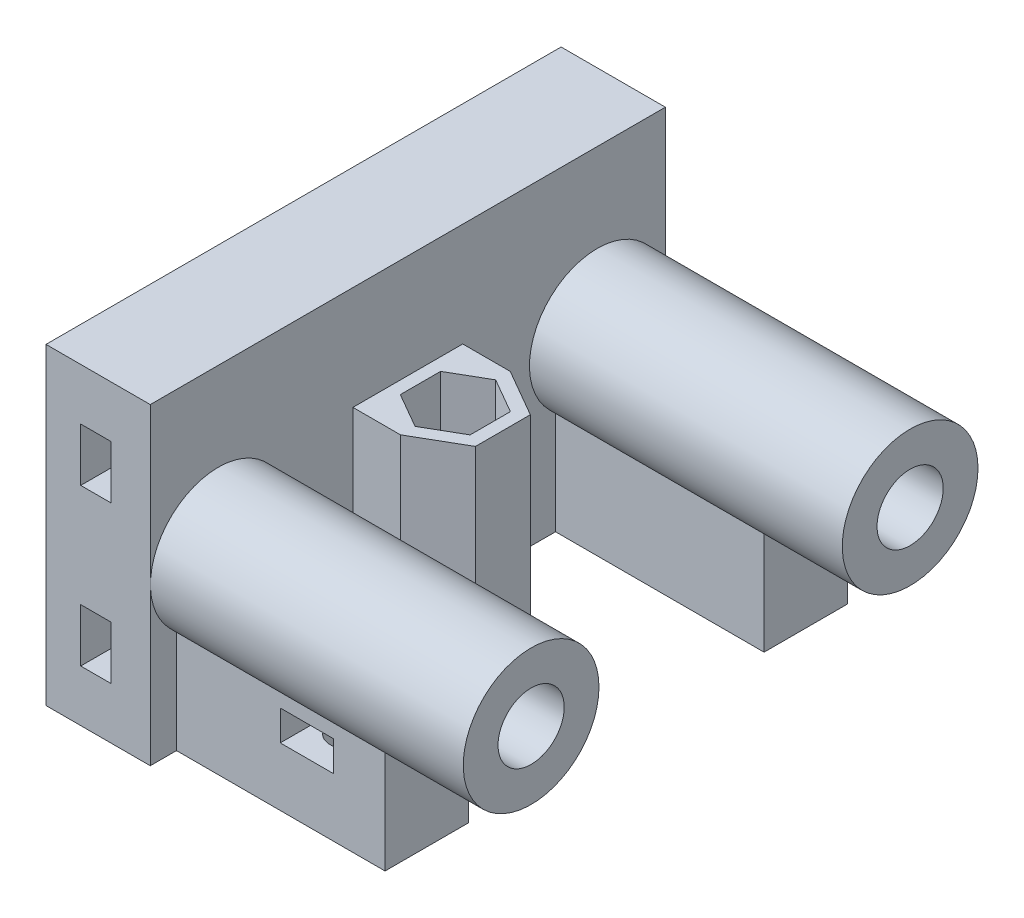
SolidWorks part; units mm, degrees
ref_plane "Front Plane" through (0, 0, 0) normal (0, 0, 1) x (1, 0, 0)
ref_plane "Top Plane" through (0, 0, 0) normal (0, 1, 0) x (1, 0, 0)
ref_plane "Right Plane" through (0, 0, 0) normal (1, 0, 0) x (0, 0, -1)
sketch "Sketch1" plane through (0, 0, 0) normal (1, 0, 0) x (0, 0, -1)
  line L1 (0, 0) -> (88.9, 0)
  line L2 (0, 0) -> (0, 76.2)
  line L3 (0, 76.2) -> (88.9, 76.2)
  line L4 (88.9, 0) -> (88.9, 76.2)
  dimension "D1" = 76.2
  dimension "D2" = 88.9
extrude "Boss-Extrude1" add sketch "Sketch1" along normal blind 25.4
sketch "Sketch2" plane through (0, 0, 0) normal (-1, 0, 0) x (0, 0, 1)
  line L0 (-88.9, 0) -> (-88.9, 76.2) construction
  line L1 (-85.09, 19.05) -> (-88.9, 19.05) construction
  line L2 (-85.09, 57.15) -> (-88.9, 57.15) construction
  line L3 (-44.45, 76.2) -> (-44.45, 0) construction
  line L4 (-88.9, 76.2) -> (0, 76.2) construction
  line L5 (0, 0) -> (-88.9, 0) construction
  circle A0 centre (-85.09, 57.15) radius 4.1021
  circle A1 centre (-85.09, 19.05) radius 4.1021
  circle A2 centre (-3.81, 19.05) radius 4.1021
  circle A3 centre (-3.81, 57.15) radius 4.1021
  dimension "D2" = 8.2042
  dimension "d1" = 19.05
  dimension "D3" = 3.81
  dimension "D4" = 38.1
  dimension "D5" = 81.28
extrude "Cut-Extrude1" cut sketch "Sketch2" against normal blind 19.05 contours A1 | A3 | A2 | A0 region at (0, 19.05, -85.09) region at (0, 19.05, -3.81) region at (0, 57.15, -3.81)
sketch "Sketch3" plane through (0, 0, 0) normal (0, 0, 1) x (1, 0, 0)
  line L0 (0, 61.2521) -> (0, 53.0479) construction
  line L1 (0, 57.15) -> (13.716, 57.15) construction
  line L2 (6.35, 63.627) -> (13.716, 63.627)
  line L3 (6.35, 63.627) -> (6.35, 50.673)
  line L4 (6.35, 50.673) -> (13.716, 50.673)
  line L5 (0, 38.1) -> (25.4, 38.1) construction
  line L7 (25.4, 76.2) -> (25.4, 0) construction
  line L8 (13.716, 12.573) -> (13.716, 25.527)
  line L9 (0, 61.2521) -> (0, 53.0479)
  line L10 (0, 55.6298) -> (0, 20.5702) construction
  line L11 (6.35, 25.527) -> (13.716, 25.527)
  line L12 (13.716, 63.627) -> (13.716, 50.673)
  line L13 (6.35, 12.573) -> (6.35, 25.527)
  line L14 (6.35, 12.573) -> (13.716, 12.573)
  dimension "D1" = 7.366
  dimension "D2" = 12.954
  dimension "D3" = 6.35
extrude "Cut-Extrude2" [suppressed] cut sketch "Sketch3" against normal blind 12.954 contours L12 L2 L3 L4 | L13 L14 L8 L11
ref_plane "Plane1" through (0, 0, -44.45) normal (0, 0, 1) x (1, 0, 0)
mirror "Mirror1" [suppressed] about plane through (0, 0, -44.45) normal (0, 0, 1)
sketch "Sketch5" plane through (25.4, 0, 0) normal (1, 0, 0) x (0, 0, -1)
  line L0 (88.9, 0) -> (88.9, 76.2) construction
  line L1 (0, 0) -> (88.9, 0)
  line L2 (0, 0) -> (0, 0.127)
  line L3 (0, 0.127) -> (88.9, 0.127)
  line L4 (88.9, 0) -> (88.9, 0.127)
  dimension "D1" = 0.127
extrude "Boss-Extrude2" add sketch "Sketch5" along normal blind 50.8
sketch "Sketch6" plane through (25.4, 0, 0) normal (1, 0, 0) x (0, 0, -1)
  line L0 (-1.7145, 38.1635) -> (90.6145, 38.1635) construction
  line L3 (44.45, 76.2) -> (44.45, 0.127) construction
  line L4 (88.9, 76.2) -> (0, 76.2) construction
  line L5 (88.9, 0.127) -> (0, 0.127) construction
  line L6 (-1.7145, 38.1635) -> (-1.7145, 54.6947) construction
  circle A0 centre (-1.7145, 38.1635) radius 8.0645
  circle A1 centre (-1.7145, 38.1635) radius 16.5312
  circle A2 centre (90.6145, 38.1635) radius 8.0645
  circle A3 centre (90.6145, 38.1635) radius 16.5312
  point P8 (44.45, 38.1635)
  point P9 (44.45, 38.1635)
  dimension "D2" = 16.129
  dimension "D3" = 8.4667
  dimension "D5" = 33.0623
  dimension "D4" = 16.5312
  dimension "V2" = 92.329
extrude "Boss-Extrude3" add sketch "Sketch6" along normal blind 76.2
sketch "Sketch7" plane through (0, 0, 0) normal (0, 0, 1) x (1, 0, 0)
  line L0 (25.4, 0.127) -> (25.4, 0)
  line L1 (0, 20.5702) -> (0, 17.5298)
  line L2 (0, 58.6702) -> (0, 55.6298)
  line L4 (0, 76.2) -> (25.4, 76.2)
  line L5 (0, 76.2) -> (0, 0)
  line L6 (0, 0) -> (25.4, 0)
  line L7 (25.4, 76.2) -> (25.4, 0)
  line L9 (25.4, 21.7215) -> (25.4, 30.2834)
  line L10 (0, 76.2) -> (0, 58.6702)
  line L11 (0, 0) -> (76.2, 0)
  line L12 (76.2, 0) -> (76.2, 0.127)
  line L13 (76.2, 0.127) -> (25.4, 0.127)
  line L14 (25.4, 0.127) -> (25.4, 21.7215)
  line L15 (25.4, 21.7215) -> (25.4, 30.2834)
  line L16 (25.4, 30.2834) -> (25.4, 46.0436)
  line L17 (25.4, 30.2834) -> (25.4, 46.0436)
  line L19 (25.4, 76.2) -> (0, 76.2)
  line L20 (0, 76.2) -> (0, 58.6702)
  line L21 (0, 0) -> (76.2, 0)
  line L22 (76.2, 0) -> (76.2, 0.127)
  line L23 (76.2, 0.127) -> (25.4, 0.127)
  line L24 (25.4, 0.127) -> (25.4, 21.7215)
  line L26 (25.4, 46.0436) -> (25.4, 54.6055)
  line L27 (25.4, 46.0436) -> (25.4, 54.6055)
  line L28 (25.4, 54.6055) -> (25.4, 76.2)
  line L29 (25.4, 76.2) -> (0, 76.2)
  line L30 (25.4, 54.6055) -> (25.4, 76.2)
  line L39 (19.05, 17.5298) -> (0, 17.5298)
  line L40 (19.05, 17.5298) -> (0, 17.5298)
  line L41 (0, 17.5298) -> (0, 0)
  line L42 (0, 17.5298) -> (0, 0)
  line L43 (0, 58.6702) -> (19.05, 58.6702)
  line L44 (0, 58.6702) -> (19.05, 58.6702)
  line L45 (19.05, 58.6702) -> (19.05, 55.6298)
  line L46 (19.05, 58.6702) -> (19.05, 55.6298)
  line L47 (19.05, 55.6298) -> (0, 55.6298)
  line L48 (19.05, 55.6298) -> (0, 55.6298)
  line L49 (0, 55.6298) -> (0, 20.5702)
  line L50 (0, 55.6298) -> (0, 20.5702)
  line L51 (0, 20.5702) -> (19.05, 20.5702)
  line L52 (0, 20.5702) -> (19.05, 20.5702)
  line L53 (19.05, 20.5702) -> (19.05, 17.5298)
  line L54 (19.05, 20.5702) -> (19.05, 17.5298)
  line M15 (0, 76.2) -> (0, 58.6702)
  line M16 (0, 0) -> (76.2, 0)
  line M17 (76.2, 0) -> (76.2, 0.127)
  line M18 (76.2, 0.127) -> (25.4, 0.127)
  line M19 (25.4, 0.127) -> (25.4, 21.7215)
  line M20 (25.4, 21.7215) -> (25.4, 30.2834)
  line M21 (25.4, 30.2834) -> (25.4, 46.0436)
  line M22 (25.4, 46.0436) -> (25.4, 54.6055)
  line M23 (25.4, 54.6055) -> (25.4, 76.2)
  line M24 (25.4, 76.2) -> (0, 76.2)
  dimension "D1" = 0
extrude "Boss-Extrude4" add sketch "Sketch7" along normal blind 18.288 contours L0 M18 M16 M17 | L0 M19 M20 M21 M22 M23 M24 M15 M16 region at (50.8, 0.0635, 0) region at (12.9021, 38.1, 0)
mirror "Mirror2" about plane through (0, 0, -44.45) normal (0, 0, 1) of "Boss-Extrude4"
sketch "Sketch8" plane through (0, 0.127, 0) normal (0, 1, 0) x (1, 0, 0)
  line L0 (101.6, 14.8167) -> (25.4, 14.8167) construction
  line L1 (25.4, -18.2457) -> (101.6, -18.2457) construction
  line L2 (101.6, 14.8167) -> (25.4, 14.8167)
  line L3 (25.4, -18.2457) -> (101.6, -18.2457)
  line L4 (25.4, 107.188) -> (25.4, -18.288)
  line L5 (25.4, -18.288) -> (76.2, -18.288)
  line L6 (76.2, -18.288) -> (76.2, 107.188)
  line L7 (76.2, 107.188) -> (25.4, 107.188)
  line L8 (25.4, 107.188) -> (25.4, -18.288)
  line L9 (25.4, -18.288) -> (76.2, -18.288)
  line L10 (76.2, -18.288) -> (76.2, 107.188)
  line L11 (76.2, 107.188) -> (25.4, 107.188)
  line L13 (25.4, 14.8167) -> (76.2, 14.8167)
  line L14 (25.4, 14.8167) -> (25.4, -18.2457)
  line L15 (25.4, -18.2457) -> (76.2, -18.2457)
  line L16 (76.2, 14.8167) -> (76.2, -18.2457)
  line L17 (25.4, 8.4667) -> (76.2, 8.4667)
  line L18 (25.4, 8.4667) -> (25.4, -11.8957)
  line L19 (25.4, -11.8957) -> (76.2, -11.8957)
  line L20 (76.2, 8.4667) -> (76.2, -11.8957)
  dimension "D2" = 6.35
  dimension "D3" = 6.35
  dimension "D1" = 0
extrude "Boss-Extrude5" add sketch "Sketch8" along normal blind 27.94 contours L14 L19 L16 L17 region at (50.8, 0.127, 1.7145)
sketch "Sketch11" plane through (101.6, 0, 0) normal (1, 0, 0) x (0, 0, -1)
  circle A0 centre (-1.7145, 38.1635) radius 8.0645
  circle A1 centre (-1.7145, 38.1635) radius 8.0645 construction
extrude "Cut-Extrude5" [suppressed] cut sketch "Sketch11" against normal blind 76.2
sketch "Sketch12" plane through (0, 0, 0) normal (0, -1, 0) x (1, 0, 0)
  line L0 (101.6, -6.35) -> (101.6, 9.779) construction
  line L1 (101.6, -6.35) -> (101.6, 9.779)
  line L2 (101.6, 1.7145) -> (0, 1.7145) construction
  line L3 (0, 18.288) -> (0, -107.188) construction
  line L4 (76.2, -8.4667) -> (76.2, 11.8957) construction
  line L5 (0, 18.288) -> (76.2, 18.288) construction
  line L6 (57.15, -2.7686) -> (57.15, 18.288) construction
  circle A0 centre (57.15, 1.7145) radius 4.4831
  dimension "D2" = 8.9662
  dimension "D3" = 21.0566
  dimension "D1" = 19.05
extrude "Cut-Extrude6" cut sketch "Sketch12" against normal up to next contours L2 A0 | A0 L2 region at (57.15, 0, 1.7145)
sketch "Sketch13" plane through (0, 0, 18.288) normal (0, 0, 1) x (1, 0, 0)
  line L0 (52.6669, 0) -> (61.6331, 0) construction
  line L1 (52.6669, 0) -> (61.6331, 0)
  line L2 (57.15, 0) -> (57.15, 25.1395) construction
  line L4 (76.2, 21.6323) -> (101.6, 21.6323) construction
  line L5 (76.2, 21.6323) -> (101.6, 21.6323)
  line L6 (76.2, 25.1395) -> (25.4, 25.1395) construction
  line L7 (50.673, 21.6323) -> (63.627, 21.6323)
  line L8 (50.673, 21.6323) -> (50.673, 14.2663)
  line L9 (50.673, 14.2663) -> (63.627, 14.2663)
  line L10 (63.627, 21.6323) -> (63.627, 14.2663)
  point P12 (57.15, 21.6323)
  dimension "D1" = 7.366
  dimension "D2" = 12.954
extrude "Cut-Extrude7" cut sketch "Sketch13" against normal blind 22.9616 contours L2 L9 L10 L7 | L9 L2 L7 L8 region at (53.9115, 17.9493, 18.288) region at (60.3885, 17.9493, 18.288)
mirror "Mirror3" about plane through (0, 0, -44.45) normal (0, 0, 1) of "Cut-Extrude7", "Cut-Extrude6", "Boss-Extrude5", "Cut-Extrude5"
sketch "Sketch14" plane through (0, 0.127, 0) normal (0, 1, 0) x (1, 0, 0)
  line L0 (0, -18.288) -> (0, 107.188) construction
  line L3 (36.9816, 31.0767) -> (45.4816, 39.5425) construction
  line L4 (28.4816, 39.5425) -> (36.9816, 34.635)
  line L5 (36.9816, 34.635) -> (45.4816, 39.5425)
  line L6 (45.4816, 39.5425) -> (45.4816, 49.3575)
  line L7 (45.4816, 49.3575) -> (36.9816, 54.265)
  line L8 (36.9816, 54.265) -> (28.4816, 49.3575)
  line L9 (28.4816, 49.3575) -> (28.4816, 39.5425)
  line L10 (36.9816, 57.8233) -> (25.4, 51.1366)
  line L11 (25.4, 51.1366) -> (25.4, 37.7634)
  line L12 (25.4, 37.7634) -> (36.9816, 31.0767)
  line L13 (36.9816, 31.0767) -> (48.5632, 37.7634)
  line L14 (48.5632, 37.7634) -> (48.5632, 51.1366)
  line L15 (48.5632, 51.1366) -> (36.9816, 57.8233)
  line L16 (0, -18.288) -> (0, 107.188)
  line L17 (0, 44.45) -> (83.2282, 44.45) construction
  line L18 (25.4, 107.188) -> (25.4, -18.288) construction
  circle A0 centre (36.9816, 44.45) radius 8.5 construction
  circle A1 centre (36.9816, 44.45) radius 11.5816 construction
  circle A2 centre (36.9816, 44.45) radius 5.25
  point P4 (25.4, 44.45)
  dimension "D2" = 10.5
  dimension "D1" = 17
  dimension "D3" = 8.4658
extrude "Boss-Extrude6" add sketch "Sketch14" along normal blind 50.8 contours L14 L15 L10 L11 L12 L13 L9 L8 L7 L6 L5 L4 region at (42.5955, 0.127, -54.1736)
extrude "Cut-Extrude8" cut sketch "Sketch14<3>" against normal up to next contours A2 region at (36.9816, 0.127, -44.45)
sketch "Sketch14<3>" plane through (0, 0.127, 0) normal (0, 1, 0) x (1, 0, 0) same geometry as "Sketch14"
sketch "Sketch15" plane through (0, 0, 0) normal (0, -1, 0) x (1, 0, 0)
  line L1 (45.5316, -39.5137) -> (36.9816, -34.5773)
  line L2 (36.9816, -34.5773) -> (28.4316, -39.5137)
  line L3 (28.4316, -39.5137) -> (28.4316, -49.3863)
  line L4 (28.4316, -49.3863) -> (36.9816, -54.3227)
  line L5 (36.9816, -54.3227) -> (45.5316, -49.3863)
  line L6 (45.5316, -49.3863) -> (45.5316, -39.5137)
  circle A0 centre (36.9816, -44.45) radius 8.55 construction
  dimension "D1" = 17.1
extrude "Cut-Extrude9" cut sketch "Sketch15" against normal blind 9
sketch "Sketch16" plane through (0, 0.127, 0) normal (0, 1, 0) x (1, 0, 0)
  line L0 (36.9816, 31.0767) -> (25.4, 31.0767)
  line L1 (36.9816, 57.8233) -> (25.4, 57.8233)
  line L2 (25.4, 37.7634) -> (25.4, 8.4667) construction
  line L3 (25.4, 80.4333) -> (25.4, 51.1366) construction
  line L4 (76.2, -11.8957) -> (25.4, -11.8957)
  line L5 (76.2, -11.8957) -> (25.4, -11.8957)
  line L6 (25.4, -11.8957) -> (25.4, -18.288)
  line L7 (25.4, -11.8957) -> (25.4, -18.288)
  line L8 (25.4, -18.288) -> (76.2, -18.288)
  line L9 (25.4, -18.288) -> (76.2, -18.288)
  line L10 (76.2, -18.288) -> (76.2, -11.8957)
  line L11 (76.2, -18.288) -> (76.2, -11.8957)
  line L16 (25.4, 107.188) -> (25.4, 100.7957)
  line L17 (25.4, 100.7957) -> (76.2, 100.7957)
  line L18 (76.2, 100.7957) -> (76.2, 107.188)
  line L19 (76.2, 107.188) -> (25.4, 107.188)
  line L20 (25.4, 107.188) -> (25.4, 100.7957)
  line L21 (25.4, 100.7957) -> (76.2, 100.7957)
  line L22 (25.4, 51.1366) -> (36.9816, 57.8233)
  line L23 (36.9816, 57.8233) -> (48.5632, 51.1366)
  line L24 (48.5632, 51.1366) -> (48.5632, 37.7634)
  line L25 (48.5632, 37.7634) -> (36.9816, 31.0767)
  line L26 (36.9816, 31.0767) -> (25.4, 37.7634)
  line L27 (25.4, 37.7634) -> (25.4, 8.4667)
  line L28 (25.4, 8.4667) -> (76.2, 8.4667)
  line L29 (76.2, 8.4667) -> (76.2, 80.4333)
  line L30 (76.2, 80.4333) -> (25.4, 80.4333)
  line L31 (25.4, 80.4333) -> (25.4, 51.1366)
  line L32 (25.4, 51.1366) -> (36.9816, 57.8233)
  line L33 (36.9816, 57.8233) -> (48.5632, 51.1366)
  line L34 (48.5632, 51.1366) -> (48.5632, 37.7634)
  line L35 (48.5632, 37.7634) -> (36.9816, 31.0767)
  line L36 (36.9816, 31.0767) -> (25.4, 37.7634)
  line L37 (25.4, 37.7634) -> (25.4, 8.4667)
  line L38 (25.4, 8.4667) -> (76.2, 8.4667)
  line L39 (76.2, 8.4667) -> (76.2, 80.4333)
  line L40 (76.2, 80.4333) -> (25.4, 80.4333)
  line L41 (25.4, 80.4333) -> (25.4, 51.1366)
  line L42 (76.2, 100.7957) -> (76.2, 107.188)
  line L43 (76.2, 107.188) -> (25.4, 107.188)
  line M22 (25.4, -11.8957) -> (25.4, -18.288)
  line M23 (25.4, -18.288) -> (76.2, -18.288)
  line M24 (76.2, -18.288) -> (76.2, -11.8957)
  line M35 (76.2, -11.8957) -> (25.4, -11.8957)
  dimension "D1" = 0
  dimension "D2" = 0
  dimension "D3" = 0
extrude "Cut-Extrude10" cut sketch "Sketch16" against normal up to next contours L1 L0 | M24 M35 M22 M23 | L42 L43 L20 L21 region at (53.3977, 0.127, -44.45) region at (50.8, 0.127, 15.0918) region at (50.8, 0.127, -103.9918)
sketch "Sketch18" plane through (0, 0.127, 0) normal (0, 1, 0) x (1, 0, 0)
  line L0 (36.9816, 57.8233) -> (25.4, 57.8233) construction
  line L1 (25.4, 57.8233) -> (25.4, 51.1366) construction
  line L2 (25.4, 51.1366) -> (36.9816, 57.8233) construction
  line L3 (25.4, 37.7634) -> (25.4, 31.0767) construction
  line L4 (25.4, 31.0767) -> (36.9816, 31.0767) construction
  line L5 (36.9816, 31.0767) -> (25.4, 37.7634) construction
  line L6 (36.9816, 57.8233) -> (25.4, 57.8233)
  line L7 (25.4, 57.8233) -> (25.4, 51.1366)
  line L8 (25.4, 51.1366) -> (36.9816, 57.8233)
  line L9 (25.4, 37.7634) -> (25.4, 31.0767)
  line L10 (25.4, 31.0767) -> (36.9816, 31.0767)
  line L11 (36.9816, 31.0767) -> (25.4, 37.7634)
extrude "Boss-Extrude7" add sketch "Sketch18" along normal up to surface (50.8 mm away) up to face at (36.9816, 50.927, -44.45)
sketch "Sketch20" plane through (19.05, 0, 0) normal (-1, 0, 0) x (0, 0, 1)
  line L3 (0, 17.5298) -> (18.288, 17.5298)
  line L4 (18.288, 17.5298) -> (18.288, 20.5702)
  line L5 (18.288, 20.5702) -> (0, 20.5702)
  line L6 (0, 17.5298) -> (18.288, 17.5298)
  line L7 (18.288, 17.5298) -> (18.288, 20.5702)
  line L8 (18.288, 20.5702) -> (0, 20.5702)
  circle A0 centre (-3.81, 19.05) radius 4.1021
  arc A1 (0, 20.5702) -> (0, 17.5298) centre (-3.81, 19.05) ccw
  arc A2 (0, 20.5702) -> (0, 17.5298) centre (-3.81, 19.05) ccw
  line M6 (0, 17.5298) -> (18.288, 17.5298)
  line M7 (18.288, 17.5298) -> (18.288, 20.5702)
  line M8 (18.288, 20.5702) -> (0, 20.5702)
  dimension "D1" = 0
extrude "Boss-Extrude9" add sketch "Sketch20" along normal up to surface (19.05 mm away) contours A0 M6 M7 M8 region at (19.05, 19.05, 9.2419) up to face at (0, 38.1, -44.45)
sketch "Sketch22" plane through (0, 0, 18.288) normal (0, 0, 1) x (1, 0, 0)
  line L0 (0, 23.1521) -> (0, 14.9479) construction
  line L1 (0, 23.1521) -> (0, 14.9479)
  line L2 (0, 19.05) -> (25.4, 19.05) construction
  line L3 (8.4582, 25.527) -> (15.8242, 25.527)
  line L4 (8.4582, 25.527) -> (8.4582, 12.573)
  line L5 (8.4582, 12.573) -> (15.8242, 12.573)
  line L6 (15.8242, 25.527) -> (15.8242, 12.573)
  line L7 (25.4, 76.2) -> (25.4, 0) construction
  line L8 (0, 55.6298) -> (0, 0) construction
  point P8 (8.4582, 19.05)
  dimension "D1" = 7.366
  dimension "D2" = 12.954
  dimension "D3" = 8.4582
extrude "Cut-Extrude15" cut sketch "Sketch22" against normal blind 28.4988 contours L4 L5 L6 L3
sketch "Sketch24" plane through (0, 0, 0) normal (-1, 0, 0) x (0, 0, 1)
  line L0 (-7.9121, 28.8857) -> (-7.9121, 0) construction
  line L1 (18.288, 0) -> (-107.188, 0) construction
  line L2 (18.288, 55.6298) -> (18.288, 0) construction
  circle A0 centre (-3.81, 19.05) radius 4.1021 construction
  dimension "D1" = 26.2001
mirror "Mirror4" about plane through (0, 0, -44.45) normal (0, 0, 1) of "Cut-Extrude15", "Boss-Extrude9"
ref_plane "Plane2" through (0, 38.1, 0) normal (0, 1, 0) x (1, 0, 0)
mirror "Mirror5" about plane through (0, 38.1, 0) normal (0, 1, 0) of "Mirror4", "Cut-Extrude15", "Boss-Extrude9"
ref_plane "Plane3" through (0, 9, 0) normal (0, -1, 0) x (-1, 0, 0)
sketch "Sketch25" plane through (0, 9, 0) normal (0, -1, 0) x (-1, 0, 0)
  line L0 (-28.4316, 39.5137) -> (-28.4316, 49.3863) construction
  line L1 (-28.4316, 49.3863) -> (-36.9816, 54.3227)
  line L2 (-36.9816, 54.3227) -> (-45.5316, 49.3863)
  line L3 (-45.5316, 49.3863) -> (-45.5316, 39.5137)
  line L4 (-45.5316, 39.5137) -> (-36.9816, 34.5773)
  line L5 (-36.9816, 34.5773) -> (-28.4316, 39.5137)
  line L6 (-28.4316, 39.5137) -> (-28.4316, 49.3863)
  line L7 (-45.5316, 39.5137) -> (-36.9816, 34.5773) construction
  line L18 (-25.4, 107.188) -> (-25.4, 100.7957)
  line L19 (-25.4, 100.7957) -> (-76.2, 100.7957)
  line L20 (-76.2, 100.7957) -> (-76.2, 80.4333)
  line L21 (-76.2, 80.4333) -> (-25.4, 80.4333)
  line L22 (-25.4, 80.4333) -> (-25.4, 57.8233)
  line L23 (-25.4, 57.8233) -> (-36.9816, 57.8233)
  line L24 (-36.9816, 57.8233) -> (-48.5632, 51.1366)
  line L25 (-48.5632, 51.1366) -> (-48.5632, 37.7634)
  line L26 (-48.5632, 37.7634) -> (-36.9816, 31.0767)
  line L27 (-36.9816, 31.0767) -> (-25.4, 31.0767)
  line L28 (-25.4, 31.0767) -> (-25.4, 8.4667)
  line L29 (-25.4, 8.4667) -> (-76.2, 8.4667)
  line L30 (-76.2, 8.4667) -> (-76.2, -11.8957)
  line L31 (-76.2, -11.8957) -> (-25.4, -11.8957)
  line L32 (-25.4, -11.8957) -> (-25.4, -18.288)
  line L33 (-25.4, -18.288) -> (0, -18.288)
  line L34 (0, -18.288) -> (0, 107.188)
  line L35 (0, 107.188) -> (-25.4, 107.188)
  line L36 (-25.4, 107.188) -> (-25.4, 100.7957)
  line L37 (-25.4, 100.7957) -> (-76.2, 100.7957)
  line L38 (-76.2, 100.7957) -> (-76.2, 80.4333)
  line L39 (-76.2, 80.4333) -> (-25.4, 80.4333)
  line L40 (-25.4, 80.4333) -> (-25.4, 57.8233)
  line L41 (-25.4, 57.8233) -> (-36.9816, 57.8233)
  line L42 (-36.9816, 57.8233) -> (-48.5632, 51.1366)
  line L43 (-48.5632, 51.1366) -> (-48.5632, 37.7634)
  line L44 (-48.5632, 37.7634) -> (-36.9816, 31.0767)
  line L45 (-36.9816, 31.0767) -> (-25.4, 31.0767)
  line L46 (-25.4, 31.0767) -> (-25.4, 8.4667)
  line L47 (-25.4, 8.4667) -> (-76.2, 8.4667)
  line L48 (-76.2, 8.4667) -> (-76.2, -11.8957)
  line L49 (-76.2, -11.8957) -> (-25.4, -11.8957)
  line L50 (-25.4, -11.8957) -> (-25.4, -18.288)
  line L51 (-25.4, -18.288) -> (0, -18.288)
  line L52 (0, -18.288) -> (0, 107.188)
  line L53 (0, 107.188) -> (-25.4, 107.188)
  circle A0 centre (-36.9816, 44.45) radius 8.55 construction
  circle A1 centre (-36.9816, 44.45) radius 5.125
  dimension "D2" = 10.25
  dimension "D1" = 0
extrude "Boss-Extrude10" add sketch "Sketch25" against normal blind 6.35 contours L5 L6 L1 L2 L3 L4 A1 region at (28.6928, 9, -44.45)
equation "\"d1\"= 0.75"
equation "\"d1@Sketch2\"  = \"d1\""
equation "\"V1\"= \"D2@Sketch6\""
equation "\"V2\"= \"V1\" + 3"
